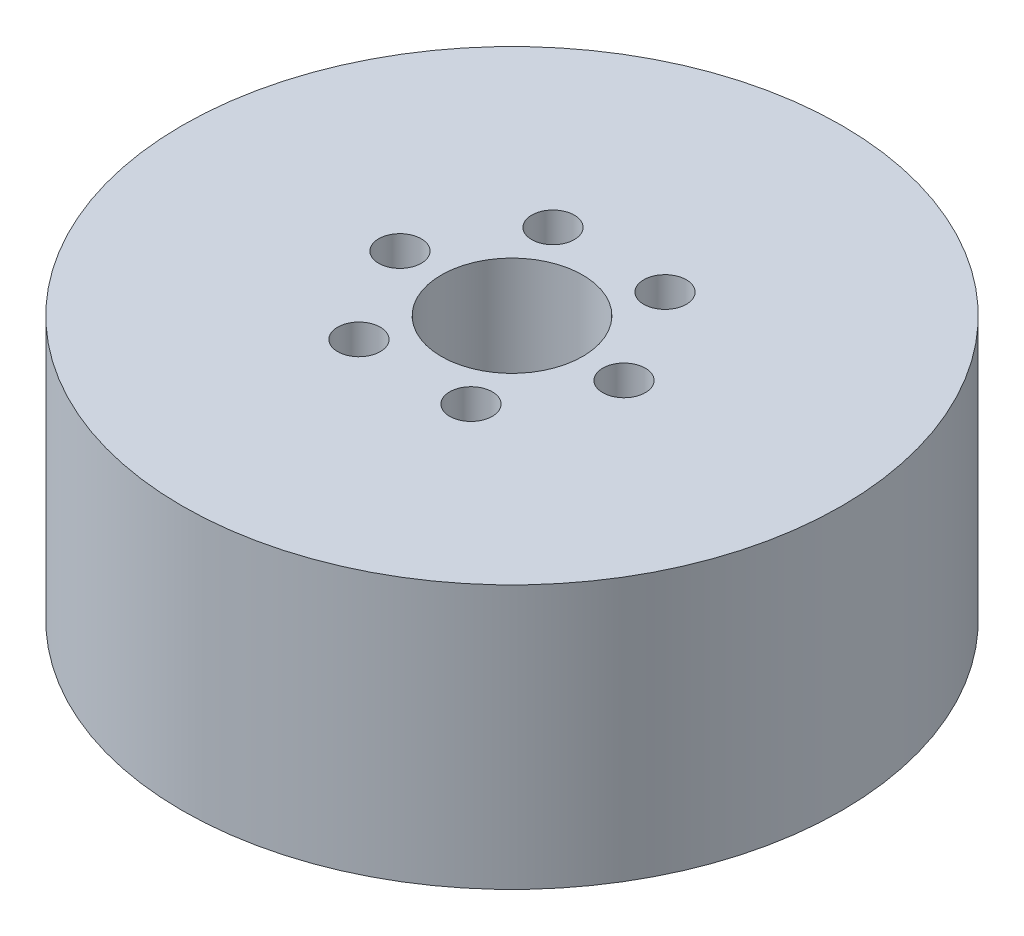
SolidWorks part; units mm, degrees
ref_plane "Front Plane" through (0, 0, 0) normal (0, 0, 1) x (1, 0, 0)
ref_plane "Top Plane" through (0, 0, 0) normal (0, 1, 0) x (1, 0, 0)
ref_plane "Right Plane" through (0, 0, 0) normal (1, 0, 0) x (0, 0, -1)
sketch "Sketch1" plane through (0, 0, 0) normal (0, 1, 0) x (1, 0, 0)
  circle A0 centre (0, 0) radius 35
  dimension "FLANGE_OD" = 70
extrude "Boss-Extrude1" add sketch "Sketch1" along normal blind 28
sketch "Sketch2" plane through (0, 0, 0) normal (0, 1, 0) x (1, 0, 0)
  circle A0 centre (0, 0) radius 7.5
  dimension "BORE_D" = 15
extrude "Cut-Extrude1" cut sketch "Sketch2" along normal through all
sketch "Sketch3" plane through (0, 28, 0) normal (0, 1, 0) x (1, 0, 0)
  circle A0 centre (0, 0) radius 11.8928 construction
  circle A1 centre (-11.8928, 0) radius 2.2612
  dimension "BOLT_D" = 4.5223
  dimension "BOLT_PCD" = 23.7855
extrude "Cut-Extrude2" cut sketch "Sketch3" against normal blind 26.039
pattern_circular "CirPattern1" count 6 over 360 about axis through (0, 0, 0) along (0, 1, 0) of "Cut-Extrude2"
